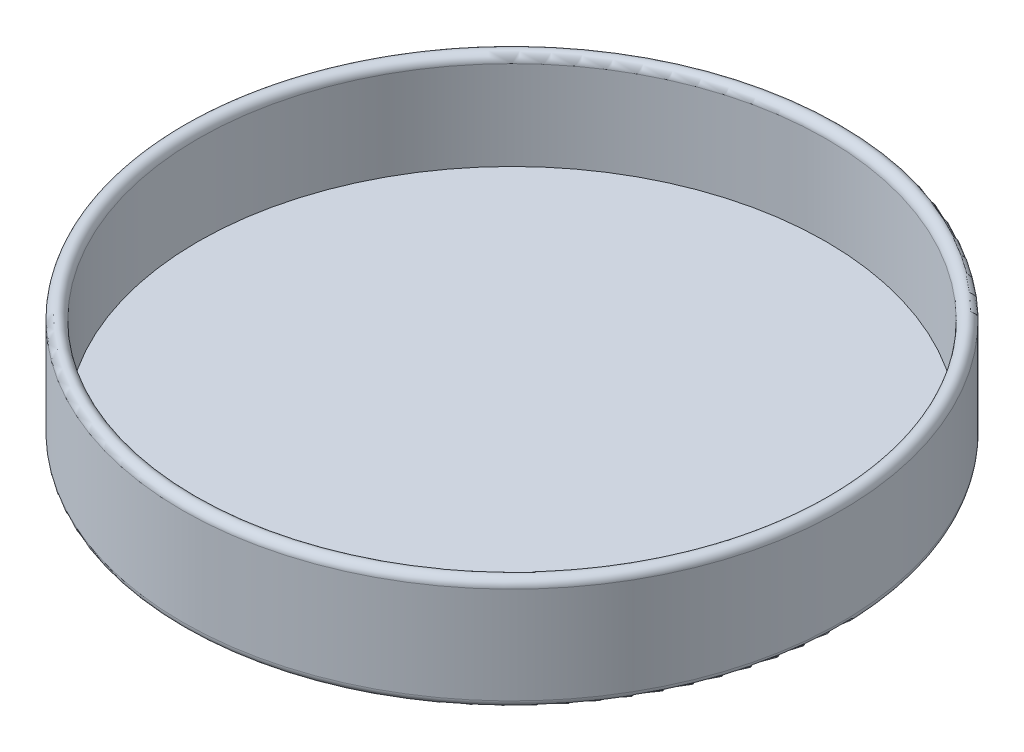
SolidWorks part; units mm, degrees
ref_plane "Front" through (0, 0, 0) normal (0, 0, 1) x (1, 0, 0)
ref_plane "Top" through (0, 0, 0) normal (0, 1, 0) x (1, 0, 0)
ref_plane "Right" through (0, 0, 0) normal (1, 0, 0) x (0, 0, -1)
sketch "Sketch1" plane through (0, 0, 0) normal (0, 1, 0) x (1, 0, 0)
  circle A0 centre (0, 0) radius 47
extrude "Boss-Extrude1" add sketch "Sketch1" along normal blind 16
sketch "Sketch2" plane through (0, 16, 0) normal (0, 1, 0) x (1, 0, 0)
  circle A0 centre (0, 0) radius 44.8
  circle A1 centre (0, 0) radius 47 construction
  dimension "D1" = 2.2
extrude "Cut-Extrude1" cut sketch "Sketch2" against normal blind 13.8
fillet "Fillet1" 2 edges at (0, 16, 47) (0, 16, 44.8) type full round first side face at (0, 16, 47) second side face at (0, 2.2, 44.8) middle face at (0, 16, 44.8)
fillet "Fillet2" radius 1.1 1 edges at (0, 0, 47)
